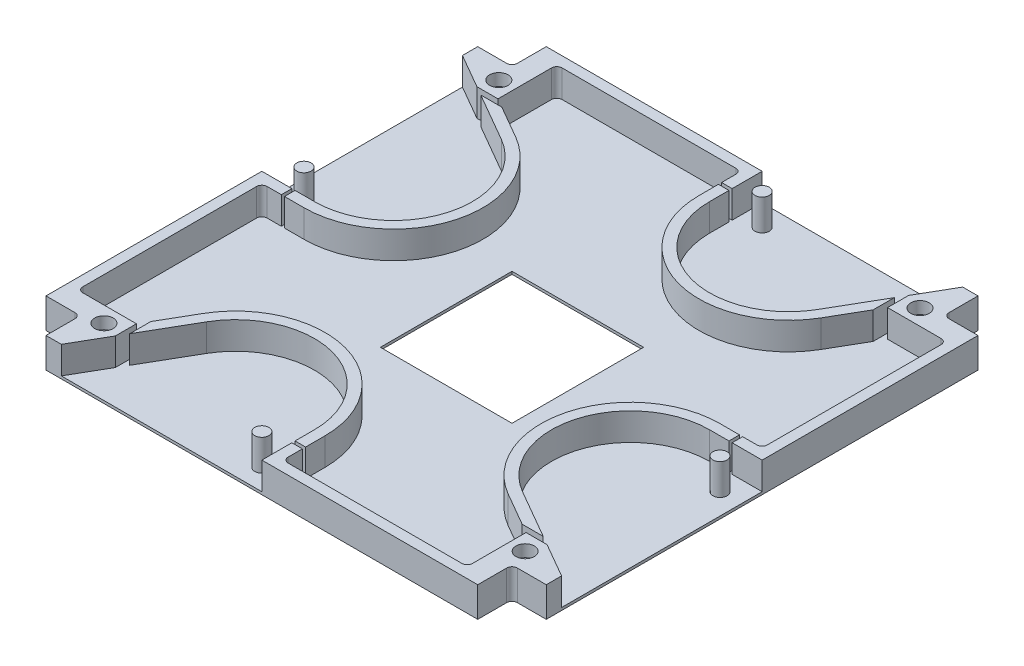
SolidWorks part; units mm, degrees
material "7075-T6 (SN)"
ref_plane "Front Plane" through (0, 0, 0) normal (0, 0, 1) x (1, 0, 0)
ref_plane "Top Plane" through (0, 0, 0) normal (0, 1, 0) x (1, 0, 0)
ref_plane "Right Plane" through (0, 0, 0) normal (1, 0, 0) x (0, 0, -1)
sketch "Sketch1" plane through (0, 0, 0) normal (0, 1, 0) x (1, 0, 0)
  line L0 (0, 0) -> (0, 6.51)
  line L21 (0, 6.51) -> (82, 6.51)
  line L22 (82, 6.51) -> (82, 0)
  line L23 (82, 0) -> (88.51, 0)
  line L24 (88.51, 0) -> (88.51, -82)
  line L25 (88.51, -82) -> (82, -82)
  line L26 (82, -82) -> (82, -88.51)
  line L27 (82, -88.51) -> (0, -88.51)
  line L28 (0, -88.51) -> (0, -82)
  line L29 (0, -82) -> (-6.51, -82)
  line L30 (-6.51, -82) -> (-6.51, 0)
  line L31 (-6.51, 0) -> (0, 0)
  dimension "D1" = 82
  dimension "D2" = 6.51
extrude "Boss-Extrude1" add sketch "Sketch1" along normal blind 0.5
sketch "Sketch2" plane through (0, 0.5, 0) normal (0, 1, 0) x (1, 0, 0)
  line L0 (-6.51, 0) -> (-6.51, -82) construction
  line L1 (0, 6.51) -> (41, 6.51)
  line L2 (0, 6.51) -> (0, 4.51)
  line L3 (0, 4.51) -> (41, 4.51)
  line L4 (41, 6.51) -> (41, 4.51)
  line L5 (88.51, 0) -> (86.51, 0)
  line L6 (88.51, 0) -> (88.51, -41)
  line L7 (88.51, -41) -> (86.51, -41)
  line L8 (86.51, 0) -> (86.51, -41)
  line L9 (82, -88.51) -> (41, -88.51)
  line L10 (82, -88.51) -> (82, -86.51)
  line L11 (82, -86.51) -> (41, -86.51)
  line L12 (41, -88.51) -> (41, -86.51)
  line L13 (-6.51, -82) -> (-4.51, -82)
  line L14 (-6.51, -82) -> (-6.51, -41)
  line L15 (-6.51, -41) -> (-4.51, -41)
  line L16 (-4.51, -82) -> (-4.51, -41)
  line L17 (-6.51, -82) -> (0, -82) construction
  line L18 (41, -3.49) -> (41, 28.4809) construction
  line L19 (56, 11.51) -> (70.2074, 11.51) construction
  line L20 (82, 6.51) -> (0, 6.51) construction
  line L21 (68.9904, -10.99) -> (79.094, 6.51)
  line L22 (79.094, 6.51) -> (82, 6.51)
  line L23 (82, 6.51) -> (82, 0)
  line L24 (82, 0) -> (86.51, 0)
  line L25 (41, 4.51) -> (41, -3.49)
  line L26 (86.51, -4) -> (75.3355, -4)
  line L27 (39, 4.51) -> (39, -3.49)
  line L28 (72.3908, -8) -> (73.0261, -8)
  line L29 (73.0261, -8) -> (70.7224, -11.99)
  line L30 (73.0261, -8) -> (75.3355, -4)
  line L31 (75.3355, -4) -> (75.3355, 0)
  line L32 (74.3355, -1.7321) -> (74.3355, -5.7321)
  circle A0 centre (56, -3.49) radius 15
  circle A1 centre (56, -3.49) radius 17 construction
  arc A2 (70.7224, -11.99) -> (39, -3.49) centre (56, -3.49) cw
  line M24 (88.51, -82) -> (88.51, 0)
  line M25 (88.51, 0) -> (82, 0)
  line M26 (82, 0) -> (82, 6.51)
  line M27 (82, 6.51) -> (0, 6.51)
  line M28 (0, 6.51) -> (0, 0)
  dimension "D3" = 30
  dimension "D6" = 34
  dimension "D1" = 41
  dimension "D2" = 2
  dimension "D4" = 30
  dimension "D7" = 4
  dimension "D8" = 4
  dimension "D5" = 5
  dimension "D9" = 1
extrude "Boss-Extrude2" add sketch "Sketch2" along normal blind 5.2 contours L4 L3 M27 M28 | A2 L29 L28 L21 A0 L25 L3 L27 | L8 L7 M25 M24 | L26 L8 L21 M25 M26 M27 region at (20.5, 0.5, -5.51) region at (40.5671, 0.5, -0.51) region at (80.332, 0.5, 0.0167) region at (87.51, 0.5, 20.5)
sketch "Sketch3" [suppressed] plane through (0, 0.5, 0) normal (0, 1, 0) x (1, 0, 0)
  line L0 (35.5217, -6.4679) -> (39.51, -26.4679)
  line L1 (39.51, -26.4679) -> (39.51, -29.4679)
  line L2 (39.51, -29.4679) -> (79.51, -29.4679)
  line L3 (79.51, -29.4679) -> (79.51, -26.4679)
  line L4 (79.51, -26.4679) -> (83.4983, -6.4679)
  line L6 (35.5217, -6.4679) -> (39.5217, -6.4679)
  line L7 (83.4983, -6.4679) -> (79.4983, -6.4679)
  line L9 (89.51, -41) -> (89.51, 0) construction
  arc A0 (79.4983, -6.4679) -> (39.5217, -6.4679) centre (59.51, -5.7836) cw
  circle A1 centre (58.485, 0) radius 15 construction
  dimension "D3" = 20
  dimension "D7" = 30
  dimension "D1" = 3
  dimension "D2" = 4
  dimension "D4" = 20
  dimension "D5" = 40
  dimension "D6" = 10
extrude "Boss-Extrude3" [suppressed] add sketch "Sketch3" along normal blind 6
ref_plane "Plane1" through (41, 0, 41) normal (0.7071, 0, 0.7071) x (0.7071, 0, -0.7071)
ref_plane "Plane2" through (0, 0, 0) normal (0.7071, 0, -0.7071) x (-0.7071, 0, -0.7071)
ref_axis "Axis1" through (41, -0.325, 41) along (0, 1, 0)
pattern_circular "CirPattern1" count 4 every 90 about axis through (41, -0.325, 41) along (0, 1, 0) of "Boss-Extrude2"
sketch "Sketch4" plane through (0, 0, 0) normal (0, -1, 0) x (1, 0, 0)
  line L0 (78, -6.51) -> (78, -0.51) construction
  line L1 (82, -6.51) -> (0, -6.51) construction
  line L2 (82, 0) -> (82, -6.51) construction
  line L3 (88.51, 78) -> (82.51, 78) construction
  line L4 (88.51, 82) -> (88.51, 0) construction
  line L5 (4, 88.51) -> (4, 82.51) construction
  line L6 (0, 88.51) -> (82, 88.51) construction
  line L7 (-6.51, 4) -> (-0.51, 4) construction
  line L8 (-6.51, 0) -> (-6.51, 82) construction
  line L10 (82, 82) -> (88.51, 82) construction
  line L11 (0, 82) -> (0, 88.51) construction
  line L12 (0, 0) -> (-6.51, 0) construction
  point P7 (78, -0.51)
  dimension "D1" = 6
  dimension "D2" = 4
  dimension "D3" = 4
  dimension "D4" = 4
  dimension "D5" = 4
  dimension "D6" = 6
  dimension "D7" = 6
  dimension "D8" = 6
sketch "Sketch8" plane through (0, 0.5, 0) normal (0, 1, 0) x (1, 0, 0)
  line L0 (2.906, -88.51) -> (41, -88.51) construction
  line L1 (41, -88.51) -> (41, -78.51) construction
  circle A0 centre (37, -84.51) radius 1.35
  dimension "D1" = 2.7
  dimension "D2" = 4
  dimension "D3" = 4
extrude "Boss-Extrude4" add sketch "Sketch8" along normal blind 5.9
pattern_circular "CirPattern2" count 4 over 360 about axis through (41, -0.325, 41) along (0, 1, 0) of "Boss-Extrude4"
fillet "Fillet1" radius 1 8 edges at (-4.51, 3.1, 78) (-4.51, 3.1, 43) (4, 3.1, -4.51) (39, 3.1, -4.51) (86.51, 3.1, 4) (86.51, 3.1, 39) (78, 3.1, 86.51) (43, 3.1, 86.51)
sketch "Sketch11" plane through (0, 0.5, 0) normal (0, 1, 0) x (1, 0, 0)
  line L0 (53.5, -53.5) -> (53.5, -28.5)
  line L1 (53.5, -28.5) -> (28.5, -28.5)
  line L2 (28.5, -28.5) -> (28.5, -53.5)
  line L3 (28.5, -53.5) -> (53.5, -53.5)
  dimension "D1" = 25
  dimension "D2" = 25
  dimension "D3" = 28.5
  dimension "D4" = 28.5
extrude "Cut-Extrude2" cut sketch "Sketch11" against normal through all
sketch "Sketch14" plane through (0, 6.4, 0) normal (0, 1, 0) x (1, 0, 0)
  point P0 (37, -84.51)
sketch "Sketch15" plane through (0, 5.7, 0) normal (0, 1, 0) x (1, 0, 0)
  line L0 (82, -82) -> (88.51, -82) construction
  line L2 (78, -85.51) -> (78, -75.3355) construction
  circle A0 centre (81, -78.5) radius 0.9
  circle A1 centre (78.5, -1) radius 0.9
  circle A2 centre (1, -3.5) radius 0.9
  circle A3 centre (3.5, -81) radius 0.9
  point P0 (1, -3.5)
  point P1 (1, -3.5)
  point P2 (3.5, -81)
  point P3 (81, -78.5)
  point P4 (78.5, -1)
  point P5 (3.5, -81)
  dimension "D3" = 1.8
  dimension "D4" = 1.8
  dimension "D5" = 1.8
  dimension "D6" = 1.8
  dimension "D1" = 3.5
  dimension "D2" = 3
extrude "Cut-Extrude3" cut sketch "Sketch15" against normal through all
sketch "Sketch16" plane through (0, 5.7, 0) normal (0, 1, 0) x (1, 0, 0)
  circle A0 centre (78.5, -1) radius 1.75
  circle A1 centre (81, -78.5) radius 1.75
  circle A2 centre (3.5, -81) radius 1.75
  circle A3 centre (1, -3.5) radius 1.75
  dimension "D1" = 3.5
  dimension "D2" = 3.5
  dimension "D3" = 3.5
  dimension "D4" = 3.5
extrude "Cut-Extrude4" cut sketch "Sketch16" against normal blind 2.3
hole_wizard "CBORE for M1.6 SHCS2" positions "3DSketch2" profile "Sketch18" counterbore size "M1.6" standard "ANSI Metric" end condition through all
sketch3d "3DSketch2"
  line L0 (81, 0, 78.5) -> (81, 3.4, 78.5) construction
  line L1 (78.5, 0, 1) -> (78.5, 3.4, 1) construction
  line L2 (1, 0, 3.5) -> (1, 3.4, 3.5) construction
  line L3 (3.5, 0, 81) -> (3.5, 3.4, 81) construction
  point P0 (81, 0, 78.5)
  point P4 (78.5, 0, 1)
  point P8 (1, 0, 3.5)
  point P12 (3.5, 0, 81)
sketch "Sketch18" plane through (81, 0, 78.5) normal (1, 0, 0) x (0, 0, -1)
  line L0 (0, 0) -> (0, 6.4)
  line L1 (0, 6.4) -> (0.9, 6.4)
  line L3 (0.9, 6.4) -> (0.9, 1.6)
  line L4 (0.9, 1.6) -> (1.75, 1.6)
  line L5 (1.75, 1.6) -> (1.75, 0)
  line L7 (1.75, 0) -> (0, 0)
  line L11 (0, -6.35) -> (0, 107.95) construction
  dimension "Thru Hole Dia." = 1.8
  dimension "Thru Hole Depth" = 6.4
  dimension "C'Bore Dia." = 3.5
  dimension "C'Bore Depth" = 1.6
ref_axis "Axis2" through (41, 6.825, 41) along (0, -1, 0)
sketch "Sketch21" plane through (0, 0.5, 0) normal (0, 1, 0) x (1, 0, 0)
  line L0 (2.906, -88.51) -> (41, -88.51) construction
  line L1 (40.5859, -82.81) -> (43.2323, -82.81)
  line L2 (40.5859, -82.81) -> (40.5859, -82.21)
  line L3 (40.5859, -82.21) -> (43.2323, -82.21)
  line L4 (43.2323, -82.81) -> (43.2323, -82.21)
  dimension "D1" = 0.6
  dimension "D2" = 5.7
extrude "Cut-Extrude5" cut sketch "Sketch21" along normal up to surface (5.2 mm away)
pattern_circular "CirPattern4" count 4 over 360 about axis through (41, 6.825, 41) along (0, -1, 0) of "Cut-Extrude5"
fillet "Fillet2" radius 1 4 edges at (82, 2.85, 0) (82, 2.85, 82) (0, 2.85, 82) (0, 2.85, 0)
equation "\"D6@Sketch2\"=\"D3@Sketch2\"+4"
equation "\"D3@Sketch4\"=\"D2@Sketch4\""
equation "\"D4@Sketch4\"=\"D3@Sketch4\""
equation "\"D5@Sketch4\"=\"D4@Sketch4\""
equation "\"D6@Sketch4\"=\"D1@Sketch4\""
equation "\"D7@Sketch4\"=\"D6@Sketch4\""
equation "\"D8@Sketch4\"=\"D7@Sketch4\""
